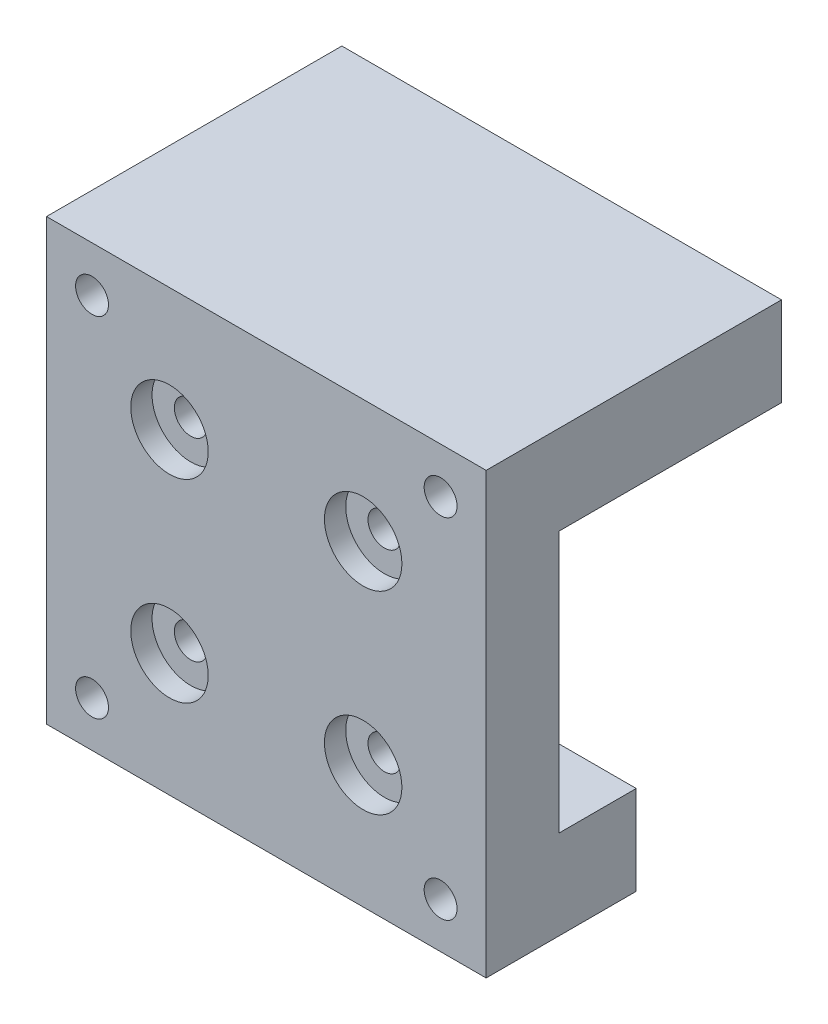
SolidWorks part; units mm, degrees
ref_plane "Front Plane" through (0, 0, 0) normal (0, 0, 1) x (1, 0, 0)
ref_plane "Top Plane" through (0, 0, 0) normal (0, 1, 0) x (1, 0, 0)
ref_plane "Right Plane" through (0, 0, 0) normal (1, 0, 0) x (0, 0, -1)
sketch "Sketch1" plane through (0, 0, 0) normal (0, 0, 1) x (1, 0, 0)
  line L1 (0, 0) -> (45.4, 0)
  line L2 (0, 0) -> (0, 45.4)
  line L3 (0, 45.4) -> (45.4, 45.4)
  line L4 (45.4, 0) -> (45.4, 45.4)
  dimension "D1" = 45.4
  dimension "D2" = 45.4
extrude "Boss-Extrude1" add sketch "Sketch1" along normal blind 15.5
ref_plane "Plane1" through (0, 0, 12.5) normal (0, 0, 1) x (1, 0, 0)
sketch "Sketch2" plane through (0, 0, 0) normal (0, 0, -1) x (-1, 0, 0)
  line L0 (-45.4, 0) -> (-45.4, 45.4) construction
  line L1 (-45.4, 36.2) -> (0, 36.2)
  line L2 (-45.4, 36.2) -> (-45.4, 9.2)
  line L3 (-45.4, 9.2) -> (0, 9.2)
  line L4 (0, 36.2) -> (0, 9.2)
  line L5 (0, 45.4) -> (0, 0) construction
  line L6 (-45.4, 22.7) -> (0, 22.7) construction
  point P13 (-45.4, 22.7)
  dimension "D1" = 27
extrude "Cut-Extrude1" cut sketch "Sketch2" against normal blind 8
sketch "Sketch19" plane through (0, 0, 0) normal (0, 0, -1) x (-1, 0, 0)
  line L0 (0, 45.4) -> (0, 36.2) construction
  line L1 (-45.4, 45.4) -> (0, 45.4)
  line L2 (-45.4, 45.4) -> (-45.4, 36.2)
  line L3 (-45.4, 36.2) -> (0, 36.2)
  line L4 (0, 45.4) -> (0, 36.2)
  line L5 (0, 36.2) -> (-45.4, 36.2) construction
extrude "Boss-Extrude2" add sketch "Sketch19" along normal blind 15
sketch "Sketch15" plane through (0, 0, 15.5) normal (0, 0, -1) x (-1, 0, 0)
  line L0 (-22.7, 45.4) -> (-22.7, 0) construction
  line L1 (-40.7, 4.7) -> (-4.7, 4.7) construction
  line L2 (-40.7, 4.7) -> (-40.7, 40.7) construction
  line L3 (-40.7, 40.7) -> (-4.7, 40.7) construction
  line L4 (-4.7, 4.7) -> (-4.7, 40.7) construction
  line L5 (-40.7, 4.7) -> (-4.7, 40.7) construction
  line L6 (-40.7, 40.7) -> (-4.7, 4.7) construction
  line L7 (-45.4, 45.4) -> (0, 45.4) construction
  line L8 (0, 0) -> (-45.4, 0) construction
  line L9 (0, 22.7) -> (-45.4, 22.7) construction
  line L12 (0, 45.4) -> (0, 0) construction
  line L13 (-45.4, 0) -> (-45.4, 45.4) construction
  circle A0 centre (-4.7, 40.7) radius 1.7
  circle A1 centre (-40.7, 40.7) radius 1.7
  circle A2 centre (-40.7, 4.7) radius 1.7
  circle A3 centre (-4.7, 4.7) radius 1.7
  point P4 (-22.7, 22.7)
  dimension "D3" = 3.4
  dimension "D1" = 36
  dimension "D2" = 36
extrude "Cut-Extrude6" cut sketch "Sketch15" along normal through all
sketch "Sketch13" plane through (0, 0, 15.5) normal (0, 0, 1) x (1, 0, 0)
  line L0 (22.7, 45.4) -> (22.7, 0) construction
  line L1 (32.7, 12.7) -> (12.7, 12.7) construction
  line L2 (32.7, 12.7) -> (32.7, 32.7) construction
  line L3 (32.7, 32.7) -> (12.7, 32.7) construction
  line L4 (12.7, 12.7) -> (12.7, 32.7) construction
  line L5 (32.7, 12.7) -> (12.7, 32.7) construction
  line L6 (32.7, 32.7) -> (12.7, 12.7) construction
  line L7 (45.4, 45.4) -> (0, 45.4) construction
  line L8 (0, 0) -> (45.4, 0) construction
  line L9 (0, 22.7) -> (45.4, 22.7) construction
  line L10 (0, 9.2) -> (0, 36.2) construction
  line L11 (45.4, 36.2) -> (45.4, 9.2) construction
  circle A4 centre (32.7, 32.7) radius 1.7
  circle A5 centre (12.7, 32.7) radius 1.7
  circle A6 centre (32.7, 12.7) radius 1.7
  circle A7 centre (12.7, 12.7) radius 1.7
  point P12 (22.7, 22.7)
  point P31 (22.7, 22.7)
  dimension "D1" = 3.4
  dimension "D2" = 20
  dimension "D3" = 20
extrude "Cut-Extrude4" cut sketch "Sketch13" against normal up to next
sketch "Sketch16" plane through (0, 0, 12.5) normal (0, 0, 1) x (1, 0, 0)
  circle A0 centre (4.7, 40.7) radius 3.5
  circle A1 centre (40.7, 40.7) radius 3.5
  circle A2 centre (40.7, 4.7) radius 3.5
  circle A3 centre (4.7, 4.7) radius 3.5
  dimension "D1" = 7
extrude "Cut-Extrude7" cut sketch "Sketch16" against normal through all
sketch "Sketch17" plane through (0, 0, 15.5) normal (0, 0, 1) x (1, 0, 0)
  line L0 (45.4, 22.7) -> (0, 22.7) construction
  line L1 (12.7, 12.7) -> (32.7, 12.7) construction
  line L2 (12.7, 12.7) -> (12.7, 32.7) construction
  line L3 (12.7, 32.7) -> (32.7, 32.7) construction
  line L4 (32.7, 12.7) -> (32.7, 32.7) construction
  line L5 (12.7, 12.7) -> (32.7, 32.7) construction
  line L6 (12.7, 32.7) -> (32.7, 12.7) construction
  line L7 (45.4, 0) -> (45.4, 45.4) construction
  line L8 (0, 45.4) -> (0, 0) construction
  line L9 (22.7, 45.4) -> (22.7, 0) construction
  line L10 (45.4, 45.4) -> (0, 45.4) construction
  line L11 (0, 0) -> (45.4, 0) construction
  circle A0 centre (12.7, 32.7) radius 4
  circle A4 centre (32.7, 32.7) radius 4
  circle A5 centre (32.7, 12.7) radius 4
  circle A6 centre (12.7, 12.7) radius 4
  point P12 (22.7, 22.7)
  point P30 (22.7, 22.7)
  dimension "D1" = 8
  dimension "D2" = 20
  dimension "D3" = 20
extrude "Cut-Extrude8" cut sketch "Sketch17" against normal blind 2.2
sketch "Sketch18" plane through (0, 0, 0) normal (0, 0, -1) x (-1, 0, 0)
  line L0 (-45.4, 4.6) -> (0, 4.6) construction
  line L1 (-45.4, 0) -> (-45.4, 9.2) construction
  line L2 (0, 9.2) -> (0, 0) construction
  circle A0 centre (-32.4, 4.6) radius 1.35
  circle A1 centre (-13, 4.6) radius 1.35
  dimension "D1" = 2.7
  dimension "D2" = 13
  dimension "D3" = 13
extrude "Cut-Extrude9" cut sketch "Sketch18" against normal blind 10
